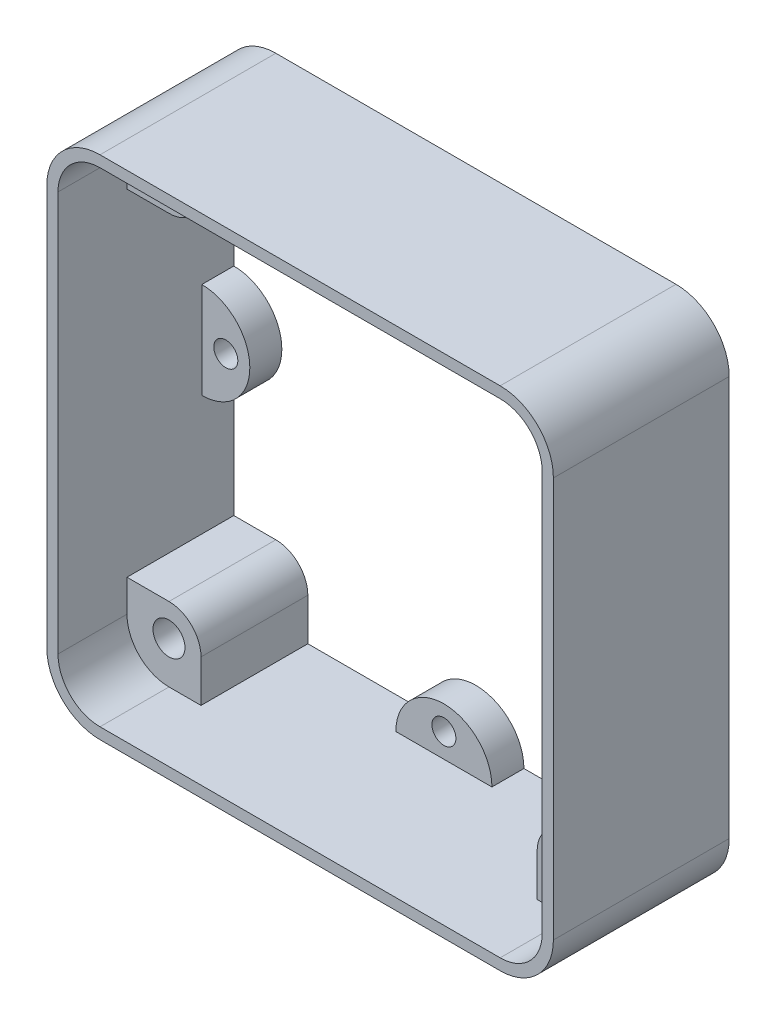
SolidWorks part; units mm, degrees
ref_plane "Front Plane" through (0, 0, 0) normal (0, 0, 1) x (1, 0, 0)
ref_plane "Top Plane" through (0, 0, 0) normal (0, 1, 0) x (1, 0, 0)
ref_plane "Right Plane" through (0, 0, 0) normal (1, 0, 0) x (0, 0, -1)
sketch "Sketch1" plane through (0, 0, 0) normal (0, 0, 1) x (1, 0, 0)
  line L0 (5, 60) -> (55, 60) construction
  line L1 (60, 55) -> (60, 5) construction
  line L2 (55, 0) -> (5, 0) construction
  line L3 (0, 5) -> (0, 55) construction
  line L4 (5, 60) -> (55, 60) construction
  line L5 (60, 55) -> (60, 5) construction
  line L6 (55, 0) -> (5, 0) construction
  line L7 (0, 5) -> (0, 55) construction
  line L8 (5, 60.25) -> (55, 60.25)
  line L9 (60.25, 55) -> (60.25, 5)
  line L10 (55, -0.25) -> (5, -0.25)
  line L11 (-0.25, 5) -> (-0.25, 55)
  line L12 (5.0003, 61.65) -> (54.9997, 61.65)
  line L13 (-1.65, 5.0003) -> (-1.65, 54.9997)
  line L14 (54.9997, -1.65) -> (5.0003, -1.65)
  line L15 (61.65, 54.9997) -> (61.65, 5.0003)
  circle A0 centre (5, 5) radius 1.6 construction
  circle A1 centre (55, 5) radius 1.6 construction
  circle A2 centre (55, 55) radius 1.6 construction
  circle A3 centre (5, 55) radius 1.6 construction
  arc A4 (60, 55) -> (55, 60) centre (55.0016, 55.0016) ccw construction
  arc A5 (55, 0) -> (60, 5) centre (55.0016, 4.9984) ccw construction
  arc A6 (0, 5) -> (5, 0) centre (4.9984, 4.9984) ccw construction
  arc A7 (5, 60) -> (0, 55) centre (4.9984, 55.0016) ccw construction
  circle A8 centre (5, 5) radius 1.6 construction
  circle A9 centre (55, 5) radius 1.6 construction
  circle A10 centre (55, 55) radius 1.6 construction
  circle A11 centre (5, 55) radius 1.6 construction
  arc A12 (60, 55) -> (55, 60) centre (55.0016, 55.0016) ccw construction
  arc A13 (55, 0) -> (60, 5) centre (55.0016, 4.9984) ccw construction
  arc A14 (0, 5) -> (5, 0) centre (4.9984, 4.9984) ccw construction
  arc A15 (5, 60) -> (0, 55) centre (4.9984, 55.0016) ccw construction
  arc A16 (60.25, 55) -> (55, 60.25) centre (55.0016, 55.0016) ccw
  arc A17 (55, -0.25) -> (60.25, 5) centre (55.0016, 4.9984) ccw
  arc A18 (-0.25, 5) -> (5, -0.25) centre (4.9984, 4.9984) ccw
  arc A19 (5, 60.25) -> (-0.25, 55) centre (4.9984, 55.0016) ccw
  arc A20 (61.65, 54.9997) -> (54.9997, 61.65) centre (55.0016, 55.0016) ccw
  arc A21 (5.0003, 61.65) -> (-1.65, 54.9997) centre (4.9984, 55.0016) ccw
  arc A22 (-1.65, 5.0003) -> (5.0003, -1.65) centre (4.9984, 4.9984) ccw
  arc A23 (54.9997, -1.65) -> (61.65, 5.0003) centre (55.0016, 4.9984) ccw
  circle A24 centre (5, 55) radius 2
  circle A25 centre (55, 55) radius 2
  circle A26 centre (55, 5) radius 2
  circle A27 centre (5, 5) radius 2
  dimension "D1" = 0.25
  dimension "D2" = 1.4
  dimension "D3" = 0.4
extrude "Boss-Extrude1" add sketch "Sketch1" along normal offset from surface 0.5 and the other way offset from surface (14.9702 mm away) 0.5 contours L14 A23 L15 A20 L12 A21 L13 A22 A19 L8 A16 L9 A17 L10 A18 L11
sketch "Sketch2" plane through (0, 0, 0) normal (0, 0, 1) x (1, 0, 0)
  line L0 (9, 55) -> (9, 60.25)
  line L1 (5, 60.25) -> (55, 60.25) construction
  line L2 (9, 60.25) -> (5, 60.25)
  line L3 (5, 51) -> (-0.25, 51)
  line L4 (-0.25, 5) -> (-0.25, 55) construction
  line L5 (-0.25, 51) -> (-0.25, 55)
  line L6 (30, 60) -> (30, 0) construction
  line L7 (60, 30) -> (0, 30) construction
  line L20 (51, 55) -> (51, 60.25)
  line L21 (55, 51) -> (60.25, 51)
  line L22 (60.25, 51) -> (60.25, 55)
  line L23 (51, 60.25) -> (55, 60.25)
  line L24 (55, 9) -> (60.25, 9)
  line L25 (51, 5) -> (51, -0.25)
  line L26 (51, -0.25) -> (55, -0.25)
  line L27 (60.25, 9) -> (60.25, 5)
  line L28 (9, 5) -> (9, -0.25)
  line L29 (5, 9) -> (-0.25, 9)
  line L30 (-0.25, 9) -> (-0.25, 5)
  line L31 (9, -0.25) -> (5, -0.25)
  arc A1 (5, 51) -> (9, 55) centre (5, 55) ccw
  circle A9 centre (5, 55) radius 2
  arc A12 (51, 55) -> (55, 51) centre (55, 55) ccw
  arc A13 (55, 9) -> (51, 5) centre (55, 5) ccw
  arc A14 (9, 5) -> (5, 9) centre (5, 5) ccw
  circle A15 centre (55, 55) radius 2
  circle A16 centre (55, 5) radius 2
  circle A17 centre (5, 5) radius 2
  spline S0 degree 3 poles (-0.25, 55) (-0.251, 58.0759) (1.9241, 60.251) (5, 60.25) knots 0 0 0 0 1 1 1 1 weights 1 0.804591 0.804591 1 construction
  spline S1 degree 3 poles (-0.25, 55) (-0.251, 58.0759) (1.9241, 60.251) (5, 60.25) knots 0 0 0 0 1 1 1 1 weights 1 0.804591 0.804591 1
  spline S3 degree 3 poles (55, 60.25) (58.0759, 60.251) (60.251, 58.0759) (60.25, 55) knots 0 0 0 0 1 1 1 1 weights 1 0.804591 0.804591 1
  spline S5 degree 3 poles (60.25, 5) (60.251, 1.9241) (58.0759, -0.251) (55, -0.25) knots 0 0 0 0 1 1 1 1 weights 1 0.804591 0.804591 1
  spline S7 degree 3 poles (5, -0.25) (1.9241, -0.251) (-0.251, 1.9241) (-0.25, 5) knots 0 0 0 0 1 1 1 1 weights 1 0.804591 0.804591 1
  point P6 (0, 0)
  point P10 (0, 0)
  point P12 (0, 0)
  point P13 (30, 30)
  point P20 (0, 0)
  point P42 (30, 30)
  point P46 (30, 30)
  point P50 (30, 30)
  point P52 (0, 0)
  dimension "D4" = 4
  dimension "D1" = 4
  dimension "D2" = 4
  dimension "D3" = 4
extrude "Boss-Extrude2" add sketch "Sketch2" along normal up to surface (13.3508 mm away) from surface at -14.9702 starting at face at (30, 30, -14.9702)
sketch "Sketch3" plane through (0, 0, 0) normal (0, 0, 1) x (1, 0, 0)
  line L0 (60.25, 24) -> (60.25, 36)
  line L1 (36, 60.25) -> (24, 60.25)
  line L5 (24, -0.25) -> (36, -0.25)
  line L6 (55, 60.25) -> (5, 60.25) construction
  line L7 (-0.25, 36) -> (-0.25, 24)
  arc A0 (24, 60.25) -> (36, 60.25) centre (30, 60.25) ccw
  circle A1 centre (30, 57.25) radius 1.5
  arc A2 (60.25, 36) -> (60.25, 24) centre (60.25, 30) ccw
  circle A3 centre (57.25, 30) radius 1.5
  arc A4 (36, -0.25) -> (24, -0.25) centre (30, -0.25) ccw
  circle A5 centre (30, 2.75) radius 1.5
  arc A6 (-0.25, 24) -> (-0.25, 36) centre (-0.25, 30) ccw
  circle A7 centre (2.75, 30) radius 1.5
  point P9 (30, 60.25)
  point P10 (30, 30)
  point P27 (30, 30)
  dimension "D1" = 6
  dimension "D2" = 3
  dimension "D3" = 3
  dimension "D4" = 4
extrude "Boss-Extrude3" add sketch "Sketch3" along normal blind 4 from surface
